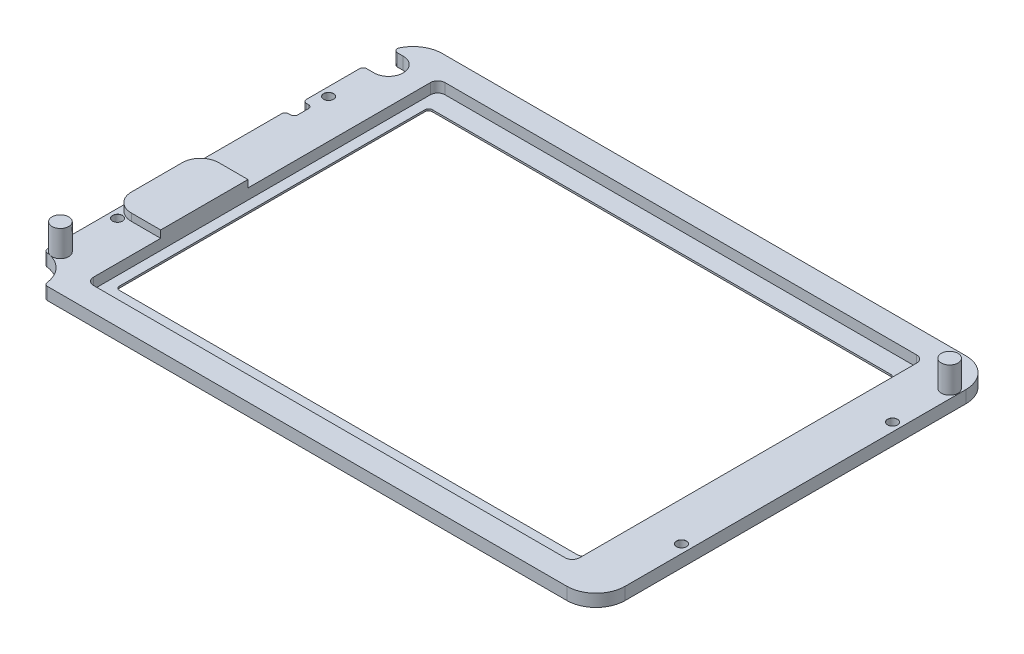
SolidWorks part; units mm, degrees
ref_plane "Front Plane" through (0, 0, 0) normal (0, 0, 1) x (1, 0, 0)
ref_plane "Top Plane" through (0, 0, 0) normal (0, 1, 0) x (1, 0, 0)
ref_plane "Right Plane" through (0, 0, 0) normal (1, 0, 0) x (0, 0, -1)
sketch "Sketch1" plane through (0, 0, 0) normal (0, 1, 0) x (1, 0, 0)
  line L1 (-79.85, 54.85) -> (79.85, 54.85)
  line L2 (-79.85, 54.85) -> (-79.85, -54.85)
  line L3 (-79.85, -54.85) -> (79.85, -54.85)
  line L4 (79.85, 54.85) -> (79.85, -54.85)
  line L5 (-79.85, 54.85) -> (79.85, -54.85) construction
  line L6 (-79.85, -54.85) -> (79.85, 54.85) construction
  point P0 (0, 0)
  dimension "D1" = 159.7
  dimension "D2" = 109.7
extrude "Boss-Extrude1" add sketch "Sketch1" along normal blind 3.4
sketch "Sketch5" plane through (0, 0, 0) normal (0, -1, 0) x (1, 0, 0)
  line L1 (-64, 43) -> (64, 43)
  line L2 (-64, 43) -> (-64, -43)
  line L3 (-64, -43) -> (64, -43)
  line L4 (64, 43) -> (64, -43)
  line L5 (-64, 43) -> (64, -43) construction
  line L6 (-64, -43) -> (64, 43) construction
  point P0 (0, 0)
  dimension "D1" = 128
  dimension "D2" = 86
extrude "Cut-Extrude1" cut sketch "Sketch5" against normal through all
sketch "Sketch6" plane through (0, 3.4, 0) normal (0, 1, 0) x (1, 0, 0)
  line L1 (-66.8, 48.3) -> (66.8, 48.3)
  line L2 (-66.8, 48.3) -> (-66.8, -48.3)
  line L3 (-66.8, -48.3) -> (66.8, -48.3)
  line L4 (66.8, 48.3) -> (66.8, -48.3)
  line L5 (-66.8, 48.3) -> (66.8, -48.3) construction
  line L6 (-66.8, -48.3) -> (66.8, 48.3) construction
  point P0 (0, 0)
  dimension "D1" = 96.6
  dimension "D2" = 133.6
extrude "Cut-Extrude2" cut sketch "Sketch6" against normal offset from surface (2.9 mm away) 0.5 up to face at (0, 0, 0)
sketch "Sketch2" plane through (0, 3.4, 0) normal (0, 1, 0) x (1, 0, 0)
  line L1 (-77.5, 29) -> (77.5, 29) construction
  line L2 (-77.5, 29) -> (-77.5, -29) construction
  line L3 (-77.5, -29) -> (77.5, -29) construction
  line L4 (77.5, 29) -> (77.5, -29) construction
  line L5 (-77.5, 29) -> (77.5, -29) construction
  line L6 (-77.5, -29) -> (77.5, 29) construction
  point P0 (0, 0)
  dimension "D1" = 155
  dimension "D2" = 58
hole_wizard "Ø2.7 (2.7) Diameter Hole1" positions "Sketch3" profile "Sketch4" hole size "Ø2.7" standard "ANSI Metric" end condition through all
sketch "Sketch3" plane through (0, 3.4, 0) normal (0, 1, 0) x (1, 0, 0)
  point P0 (-77.5, 29)
  point P3 (-77.5, -29)
  point P6 (77.5, 29)
  point P9 (77.5, -29)
sketch "Sketch4" plane through (-77.5, 3.4, -29) normal (1, 0, 0) x (0, 0, 1)
  line L0 (0, 0) -> (0, 3.4)
  line L1 (0, 3.4) -> (1.35, 3.4)
  line L2 (1.35, 3.4) -> (1.35, 0.025)
  line L3 (1.35, 0.025) -> (1.375, 0)
  line L5 (1.375, 0) -> (0, 0)
  line L6 (-1.35, 0.025) -> (-1.375, 0) construction
  line L11 (0, -6.35) -> (0, 107.95) construction
  dimension "Thru Hole Dia." = 2.7
  dimension "Thru Hole Depth" = 3.4
  dimension "Near C'Sink Dia." = 2.75
  dimension "Near C'Sink Angle" = 90
sketch "Sketch10" plane through (0, 0, 0) normal (0, -1, 0) x (1, 0, 0)
  line L1 (77.35, 44.85) -> (-77.35, 44.85) construction
  line L2 (77.35, 44.85) -> (77.35, -44.85) construction
  line L3 (77.35, -44.85) -> (-77.35, -44.85) construction
  line L4 (-77.35, 44.85) -> (-77.35, -44.85) construction
  line L5 (77.35, 44.85) -> (-77.35, -44.85) construction
  line L6 (77.35, -44.85) -> (-77.35, 44.85) construction
  circle A0 centre (-77.35, 44.85) radius 1.35
  circle A1 centre (77.35, -44.85) radius 1.35
  point P0 (0, 0)
  dimension "D3" = 2.7
  dimension "D1" = 154.7
  dimension "D2" = 89.7
extrude "Boss-Extrude3" add sketch "Sketch10" along normal blind 0.5
sketch "Sketch11" plane through (0, -0.5, 0) normal (0, -1, 0) x (1, 0, 0)
  line L1 (-77.35, 44.85) -> (77.35, 44.85) construction
  line L2 (-77.35, 44.85) -> (-77.35, -44.85) construction
  line L3 (-77.35, -44.85) -> (77.35, -44.85) construction
  line L4 (77.35, 44.85) -> (77.35, -44.85) construction
hole_wizard "M2x0.4 Tapped Hole1" positions "Sketch12" profile "Sketch13" tap size "M2x0.4" standard "ANSI Metric" end condition through all
sketch "Sketch12" plane through (0, -0.5, 0) normal (0, -1, 0) x (-1, 0, 0)
  point P0 (-77.35, 44.85)
  point P3 (77.35, -44.85)
sketch "Sketch13" plane through (77.35, -0.5, -44.85) normal (1, 0, 0) x (0, 0, -1)
  line L0 (0, 0) -> (0, 3.9)
  line L1 (0, 3.9) -> (0.8, 3.9)
  line L2 (0.8, 3.9) -> (0.8, 0.225)
  line L3 (0.8, 0.225) -> (1.025, 0)
  line L5 (1.025, 0) -> (0, 0)
  line L6 (-0.8, 0.225) -> (-1.025, 0) construction
  line L11 (0, -6.35) -> (0, 107.95) construction
  dimension "Thru Tap Drill Dia." = 1.6
  dimension "Thru Tap Drill Depth" = 3.9
  dimension "Near C'Sink Dia." = 2.05
  dimension "Near C'Sink Angle" = 90
cosmetic thread "Hole Thread1" parameters "D2"=2
cosmetic thread "Hole Thread2" parameters "D2"=2
sketch "Sketch7" plane through (0, 0, 0) normal (0, -1, 0) x (1, 0, 0)
  line L1 (-71.5, 51.1) -> (71.5, 51.1)
  line L2 (-71.5, 51.1) -> (-71.5, -51.1)
  line L3 (-71.5, -51.1) -> (71.5, -51.1)
  line L4 (71.5, 51.1) -> (71.5, -51.1)
  line L5 (-71.5, 51.1) -> (71.5, -51.1) construction
  line L6 (-71.5, -51.1) -> (71.5, 51.1) construction
  line L7 (-70.5, 50.1) -> (70.5, 50.1)
  line L8 (-70.5, 50.1) -> (-70.5, -50.1)
  line L9 (-70.5, -50.1) -> (70.5, -50.1)
  line L10 (70.5, 50.1) -> (70.5, -50.1)
  line L11 (-70.5, 50.1) -> (70.5, -50.1) construction
  line L12 (-70.5, -50.1) -> (70.5, 50.1) construction
  point P0 (0, 0)
  point P6 (0, 0)
  dimension "D1" = 143
  dimension "D2" = 102.2
  dimension "D3" = 1
  dimension "D4" = 1
extrude "Boss-Extrude2" add sketch "Sketch7" along normal blind 0.5
sketch "Sketch17" plane through (0, 0, 0) normal (0, -1, 0) x (1, 0, 0)
  line L0 (-76.85, 0) -> (76.85, 0) construction
  line L2 (-79.85, -54.85) -> (-79.85, 54.85) construction
  circle A0 centre (-76.85, 0) radius 1.5
  circle A1 centre (76.85, 0) radius 1.5
  dimension "D2" = 3
  dimension "D1" = 3
extrude "Cut-Extrude6" cut sketch "Sketch17" against normal blind 2
sketch "Sketch15" plane through (0, 3.4, 0) normal (0, 1, 0) x (1, 0, 0)
  line L0 (-79.85, 54.85) -> (-79.85, -54.85) construction
  line L1 (-79.85, 24.3) -> (-77.35, 24.3)
  line L2 (-79.85, 24.3) -> (-79.85, 19.4)
  line L3 (-79.85, 19.4) -> (-77.35, 19.4)
  line L4 (-77.35, 24.3) -> (-77.35, 19.4)
  line L5 (79.85, 54.85) -> (-79.85, 54.85) construction
  point P6 (-79.85, 21.85)
  dimension "D1" = 33
  dimension "D2" = 4.9
  dimension "D3" = 2.5
extrude "Cut-Extrude5" cut sketch "Sketch15" against normal through all
sketch "Sketch9" plane through (0, 3.4, 0) normal (0, 1, 0) x (1, 0, 0)
  line L0 (79.85, 54.85) -> (-79.85, 54.85) construction
  line L1 (-79.85, 54.85) -> (-79.85, 24.3) construction
  line L2 (-76.85, 40.85) -> (-79.85, 40.85)
  line L3 (-79.85, 40.85) -> (-79.85, 48.85)
  line L4 (-79.85, 48.85) -> (-76.85, 48.85)
  circle A0 centre (-76.85, 44.85) radius 4 construction
  arc A1 (-76.85, 48.85) -> (-76.85, 40.85) centre (-76.85, 44.85) cw
  dimension "D3" = 8
  dimension "D1" = 10
  dimension "D2" = 3
extrude "Cut-Extrude4" cut sketch "Sketch9" against normal through all
sketch "Sketch8" plane through (0, 3.4, 0) normal (0, 1, 0) x (1, 0, 0)
  line L0 (-79.85, -54.85) -> (79.85, -54.85) construction
  line L1 (-79.85, 54.85) -> (-79.85, 48.85) construction
  line L2 (-76.15, -51.15) -> (-79.85, -54.85) construction
  circle A0 centre (-76.15, -51.15) radius 1.9 construction
  circle A1 centre (-79.85, -54.85) radius 8
  dimension "D3" = 3.8
  dimension "D4" = 16
  dimension "D1" = 3.7
  dimension "D2" = 3.7
extrude "Cut-Extrude3" cut sketch "Sketch8" against normal through all
sketch "Sketch14" plane through (0, 3.4, 0) normal (0, 1, 0) x (1, 0, 0)
  circle A0 centre (-77.35, -44.85) radius 2.3
  circle A1 centre (77.35, 44.85) radius 2.3
  dimension "D1" = 4.6
extrude "Boss-Extrude4" add sketch "Sketch14" along normal blind 7.2
fillet "Fillet1" radius 8 3 edges at (79.85, 1.7, 54.85) (79.85, 1.7, -54.85) (-79.85, 1.7, -54.85)
fillet "Fillet2" radius 2 4 edges at (-70.5, -0.25, -50.1) (70.5, -0.25, -50.1) (70.5, -0.25, 50.1) (-70.5, -0.25, 50.1)
fillet "Fillet3" radius 3 4 edges at (-71.5, -0.25, -51.1) (71.5, -0.25, -51.1) (71.5, -0.25, 51.1) (-71.5, -0.25, 51.1)
fillet "Fillet4" radius 1 4 edges at (64, 0.25, 43) (-64, 0.25, 43) (64, 0.25, -43) (-64, 0.25, -43)
fillet "Fillet5" radius 2 4 edges at (-66.8, 1.95, 48.3) (66.8, 1.95, 48.3) (66.8, 1.95, -48.3) (-66.8, 1.95, -48.3)
fillet "Fillet6" radius 1 8 edges at (-71.85, 1.7, 54.85) (-79.85, 1.7, 46.85) (-79.85, 1.7, -48.85) (-79.85, 1.7, -40.85) (-79.85, 1.7, -19.4) (-77.35, 1.7, -19.4) (-77.35, 1.7, -24.3) (-79.85, 1.7, -24.3)
sketch "Sketch16" plane through (0, 3.4, 0) normal (0, 1, 0) x (1, 0, 0)
  line L0 (-79.85, 18.4) -> (-79.85, -45.9057) construction
  line L1 (-79.85, -3.85) -> (-66.8, -3.85)
  line L2 (-79.85, -3.85) -> (-79.85, -27.85)
  line L3 (-79.85, -27.85) -> (-66.8, -27.85)
  line L4 (-66.8, -3.85) -> (-66.8, -27.85)
  line L5 (-66.8, -46.3) -> (-66.8, 46.3) construction
  line L6 (-70.9057, -54.85) -> (71.85, -54.85) construction
  point P8 (-79.85, -15.85)
  dimension "D1" = 39
  dimension "D2" = 24
extrude "Boss-Extrude5" add sketch "Sketch16" along normal blind 2
fillet "Fillet7" radius 5 2 edges at (-79.85, 4.4, 3.85) (-79.85, 4.4, 27.85)
